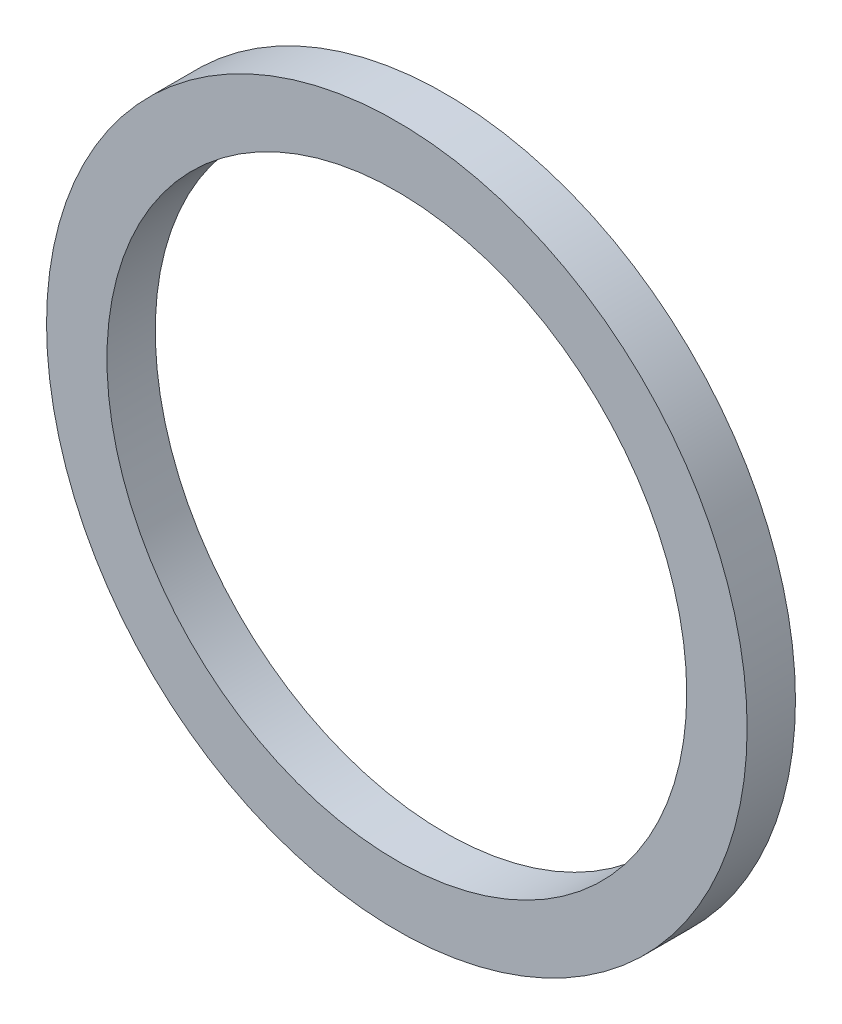
SolidWorks part; units mm, degrees
ref_plane "Front Plane" through (0, 0, 0) normal (0, 0, 1) x (1, 0, 0)
ref_plane "Top Plane" through (0, 0, 0) normal (0, 1, 0) x (1, 0, 0)
ref_plane "Right Plane" through (0, 0, 0) normal (1, 0, 0) x (0, 0, -1)
sketch "Sketch1" plane through (0, 0, 0) normal (0, 0, 1) x (1, 0, 0)
  circle A0 centre (0, 0) radius 72.5
  circle A1 centre (0, 0) radius 60
  point P5 (0, 1.8032)
  dimension "D1" = 145
  dimension "D2" = 120
extrude "Boss-Extrude1" add sketch "Sketch1" along normal blind 10
equation "\"smallPulleyTeeth\"= 15"
equation "\"largePulleyTeeth\"= 40"
equation "\"eighthThick\"= 2.9mm"
equation "\"sixteenthThick\" = 1.7mm"
equation "\"quarterThick\"=5.9mm"
equation "\"OD\" = 145mm"
equation "\"puckAngle\" = 60.5deg"
equation "\"puckDiam\" = 76.5mm"
equation "\"axlePress\" = 5.9mm"
equation "\"press\" = 0.2mm"
equation "\"wheelClear\" = 0.3mm"
equation "\"10-32clear\" = 4.5mm"
equation "\"6-32clear\" = 3.3mm"
equation "\"8-32clear\" = 4.0mm"
equation "\"wheelHeight\" = 24mm"
equation "\"wheelWell\" = 62mm"
equation "\"D1@Sketch1\"=\"OD\""
